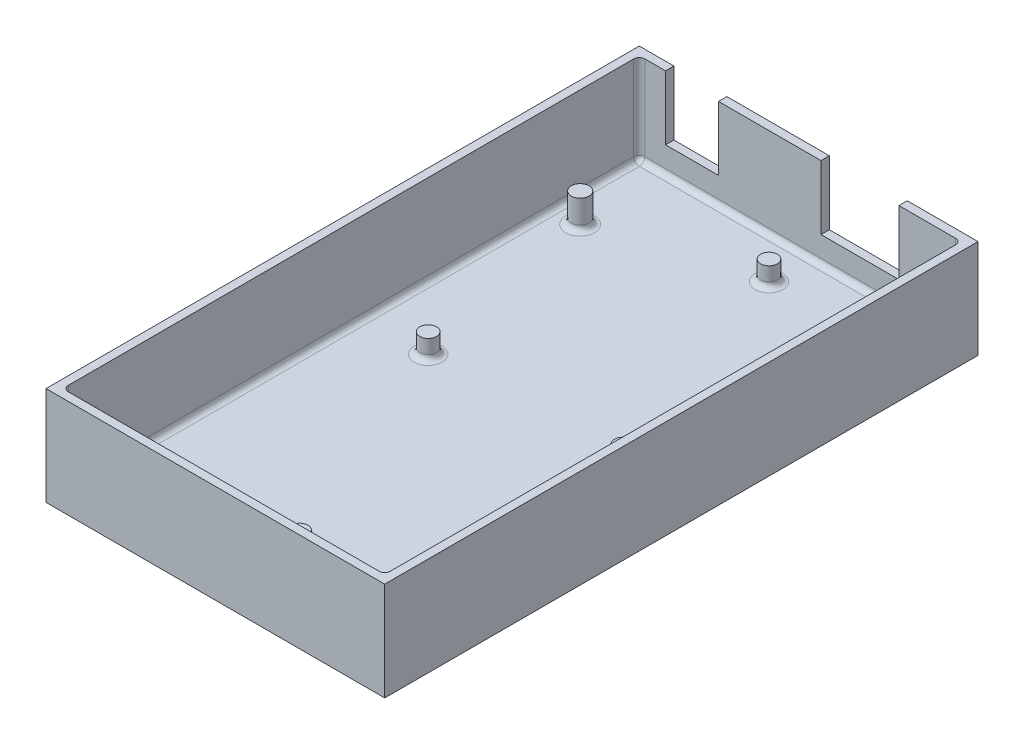
SolidWorks part; units mm, degrees
ref_plane "Front Plane" through (0, 0, 0) normal (0, 0, 1) x (1, 0, 0)
ref_plane "Top Plane" through (0, 0, 0) normal (0, 1, 0) x (1, 0, 0)
ref_plane "Right Plane" through (0, 0, 0) normal (1, 0, 0) x (0, 0, -1)
sketch "Sketch1" plane through (0, 0, 0) normal (0, 1, 0) x (1, 0, 0)
  line L0 (24.55, 14.33) -> (24.55, 20.83) construction
  line L1 (3.0629, 20.83) -> (15.05, 20.83) construction
  line L2 (-2.2, -87.17) -> (-2.2, -88.17) construction
  line L3 (24.55, 14.33) -> (15.05, 14.33) construction
  line L4 (24.55, 14.33) -> (-1.7, 14.33) construction
  line L5 (24.55, 14.33) -> (24.55, -87.17) construction
  line L6 (24.55, -87.17) -> (-28.95, -87.17) construction
  line L7 (-28.95, -87.17) -> (-28.95, 14.33) construction
  line L8 (-28.95, 14.33) -> (-1.7, 14.33) construction
  line L9 (15.05, 14.33) -> (15.05, 20.83) construction
  line L10 (3.0629, 14.0695) -> (3.0629, 20.83) construction
  line L11 (-2.2, -88.17) -> (27.25, -88.17)
  line L12 (27.25, -88.17) -> (27.25, 15.33)
  line L13 (-2.2, -88.17) -> (-30.55, -88.17)
  line L14 (-30.55, -88.17) -> (-30.55, 15.33)
  line L15 (-30.55, 15.33) -> (27.25, 15.33)
  line L16 (-2.2, -88.17) -> (-2.2, -89.67) construction
  line L17 (-2.2, -89.67) -> (-32.05, -89.67)
  line L18 (-2.2, -89.67) -> (28.75, -89.67)
  line L19 (28.75, -89.67) -> (28.75, 16.83)
  line L20 (-32.05, -89.67) -> (-32.05, 16.83)
  line L21 (-32.05, 16.83) -> (28.75, 16.83)
  circle A0 centre (22.43, -1.27) radius 1.6
  circle A1 centre (-25.83, 0) radius 1.6
  circle A2 centre (22.43, -76.2) radius 1.6
  circle A3 centre (-25.83, -82.55) radius 1.6
  dimension "D5" = 3.2
  dimension "D6" = 3.2
  dimension "D7" = 3.2
  dimension "D9" = 3.2
  dimension "D1" = 48.26
  dimension "D2" = 48.26
  dimension "D3" = 15.6
  dimension "D4" = 74.93
  dimension "D8" = 82.55
  dimension "D10" = 6.5
  dimension "D11" = 101.5
  dimension "D12" = 53.5
  dimension "D13" = 1
  dimension "D14" = 9.5
  dimension "D15" = 29.45
  dimension "D16" = 103.5
  dimension "D17" = 28.35
  dimension "D18" = 1.5
  dimension "D19" = 29.85
  dimension "D20" = 30.95
  dimension "D21" = 106.5
  dimension "D22" = 26.75
extrude "Boss-Extrude1" add sketch "Sketch1" against normal blind 1.5 from offset 3.5 contours L21 L20 L17 L18 L19 L14 L15 L12 L11 L13 | L15 L14 L13 L11 L12 A3 A2 A1 A0 | A3 | A1 | A0 | A2 region at (-1.6497, 0, 36.4006) region at (-17.125, 0, 88.4437) offset against normal yes
extrude "Boss-Extrude2" add sketch "Sketch1<3>" along normal blind 3.5 from offset 3.5 separate body contours L21 L20 L17 L18 L19 L14 L15 L12 L11 L13 region at (-17.125, 0, 88.4437) offset against normal yes
sketch "Sketch1<3>" plane through (0, 0, 0) normal (0, 1, 0) x (1, 0, 0) same geometry as "Sketch1"
extrude "Boss-Extrude3" add sketch "Sketch1<5>" along normal blind 1.7 contours L21 L20 L17 L18 L19 L14 L15 L12 L11 L13 region at (-17.125, 0, 88.4437)
sketch "Sketch1<5>" plane through (0, 0, 0) normal (0, 1, 0) x (1, 0, 0) same geometry as "Sketch1"
sketch "Sketch2" plane through (0, -3.5, 0) normal (0, 1, 0) x (1, 0, 0)
  line L0 (0, 0) -> (0, -91.3462) construction
  line L1 (22.43, -76.2) -> (-5.5383, -76.2) construction
  line L2 (-46.2052, -33.8148) -> (51.2971, -33.8148) construction
  line L3 (0, 0) -> (0, 21.5785) construction
  circle A0 centre (0, -76.2) radius 1.5
  circle A1 centre (-19.297, -33.8148) radius 1.5
  circle A2 centre (15.644, -33.8148) radius 1.5
  circle A3 centre (0, 8.0639) radius 1.5
  dimension "D1" = 3
  dimension "D2" = 3
  dimension "D3" = 3
  dimension "D4" = 3
extrude "Boss-Extrude4" add sketch "Sketch2" along normal blind 3.5
extrude "Boss-Extrude5" add sketch "Sketch1<7>" along normal blind 5.2 from offset 3.5 contours A1 | A0 | A3 | A2 region at (22.43, 0, 1.27) region at (-25.83, 0, 0) region at (-25.83, 0, 82.55) offset against normal yes
sketch "Sketch1<7>" plane through (0, 0, 0) normal (0, 1, 0) x (1, 0, 0) same geometry as "Sketch1"
fillet "Fillet5" radius 1 12 edges at (27.25, -3.5, 36.42) (-1.65, -3.5, 88.17) (-30.55, -3.5, 36.42) (-1.65, -3.5, -15.33) (0, -3.5, 77.7) (-19.297, -3.5, 35.3148) (15.644, -3.5, 35.3148) (0, -3.5, -6.5639) (-25.83, -3.5, 1.6) (22.43, -3.5, 2.87) (-25.83, -3.5, 84.15) (22.43, -3.5, 77.8)
sketch "Sketch3" plane through (0, 1.7, 0) normal (0, 1, 0) x (1, 0, 0)
  line L0 (0, 0) -> (0, 25.6693) construction
  line L1 (-25.83, 16.83) -> (-32.05, 16.83)
  line L2 (-32.05, 16.83) -> (28.75, 16.83) construction
  line L3 (2.0636, 16.83) -> (2.0636, 15.33)
  line L4 (-30.55, 15.33) -> (27.25, 15.33) construction
  line L5 (-25.83, 0) -> (-25.83, 21.0788) construction
  line L6 (-32.05, 16.83) -> (-32.05, -89.67)
  line L7 (-32.05, -89.67) -> (28.75, -89.67)
  line L8 (-30.55, 15.33) -> (27.25, 15.33) construction
  line L9 (16.0551, 16.83) -> (16.0551, 15.33)
  line L10 (-16.33, 16.83) -> (2.0636, 16.83)
  line L11 (-16.33, 16.83) -> (-16.33, 15.33)
  line L12 (-25.83, 16.83) -> (-25.83, 15.33)
  line L13 (28.75, -89.67) -> (28.75, 16.83)
  line L14 (28.75, 16.83) -> (16.0551, 16.83)
  line L15 (-16.33, 15.33) -> (2.0636, 15.33)
  line L16 (16.0551, 15.33) -> (27.25, 15.33)
  line L17 (27.25, 15.33) -> (27.25, -88.17)
  line L18 (27.25, -88.17) -> (-30.55, -88.17)
  line L19 (-30.55, -88.17) -> (-30.55, 15.33)
  line L20 (-30.55, 15.33) -> (-25.83, 15.33)
  dimension "D4" = 9.5
extrude "Boss-Extrude6" add sketch "Sketch3" along normal blind 11
sketch "Sketch4" plane through (0, 0, -16.83) normal (0, 0, -1) x (-1, 0, 0)
  line L0 (-16.0551, 1.7) -> (-16.0551, 1.2)
  line L1 (-16.0551, 1.7) -> (-2.0636, 1.7)
  line L2 (-2.0636, 1.7) -> (-2.0636, 1.2)
  line L3 (-2.0636, 1.2) -> (-16.0551, 1.2)
  line L4 (16.33, 1.7) -> (16.33, 1.2)
  line L5 (16.33, 1.7) -> (25.83, 1.7)
  line L6 (25.83, 1.7) -> (25.83, 1.2)
  line L7 (25.83, 1.2) -> (16.33, 1.2)
  dimension "D1" = 0.5
  dimension "D2" = 0.5
extrude "Cut-Extrude1" cut sketch "Sketch4" against normal blind 11
fillet "Fillet6" radius 1 8 edges at (-30.2571, -3.2071, -15.0371) (26.9571, -3.2071, -15.0371) (26.9571, -3.2071, 87.8771) (-30.2571, -3.2071, 87.8771) (-30.55, 5.1, -15.33) (27.25, 5.1, -15.33) (27.25, 5.1, 88.17) (-30.55, 5.1, 88.17)
